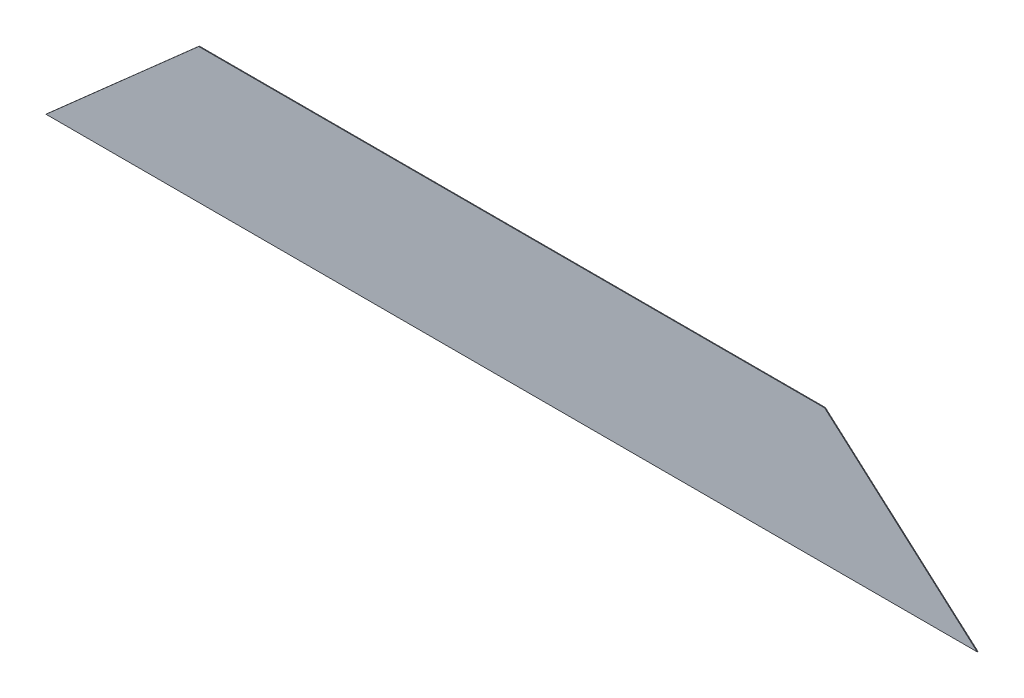
SolidWorks part; units mm, degrees
ref_plane "Alzado" through (0, 0, 0) normal (0, 0, 1) x (1, 0, 0)
ref_plane "Planta" through (0, 0, 0) normal (0, 1, 0) x (1, 0, 0)
ref_plane "Vista lateral" through (0, 0, 0) normal (1, 0, 0) x (0, 0, -1)
sketch "Croquis1" plane through (0, 0, 0) normal (0, 0, 1) x (1, 0, 0)
  line L0 (-1050.4, -140.1123) -> (-706, 164.4877)
  line L1 (-1050.4, -140.1123) -> (1050.4, -140.1123)
  line L2 (878.2, 12.1877) -> (-878.2, 12.1877) construction
  line L3 (-706, 164.4877) -> (706, 164.4877)
  line L5 (0, 164.4877) -> (0, 0) construction
  line L8 (706, 164.4877) -> (1050.4, -140.1123)
  point P0 (0, 0)
  dimension "D1" = 304.6
  dimension "D2" = 1412
  dimension "D3" = 344.4
  dimension "D4" = 344.4
base flange "Brida base1" sketch "Croquis1" thickness 1.5875 reverse thickness direction no parameters "D1"=0.7366
sketch "Líneas de pliegue1" [suppressed] plane through (0, 0, 0) normal (0, 1, 0) x (1, 0, 0)
sketch "Cuadro delimitador1" [suppressed] plane through (0, 0, 0) normal (0, 1, 0) x (1, 0, 0)
sheet metal parameters "Chapa metálica1" thickness 1.5875 parameters "D1"=0.7366
flat pattern "Chapa desplegada1" [suppressed]
sketch "Líneas de pliegue2" plane through (0, 0, 0) normal (0, 1, 0) x (1, 0, 0)
sketch3d "Cuadro delimitador2" [suppressed]
  line L0 (-1050.4, -140.1123, 0) -> (1050.4, -140.1123, 0) construction
  line L1 (-1050.4, 164.4877, 0) -> (1050.4, 164.4877, 0) construction
  line L2 (-1050.4, -140.1123, 0) -> (-1050.4, 164.4877, 0) construction
  line L3 (1050.4, -140.1123, 0) -> (1050.4, 164.4877, 0) construction
